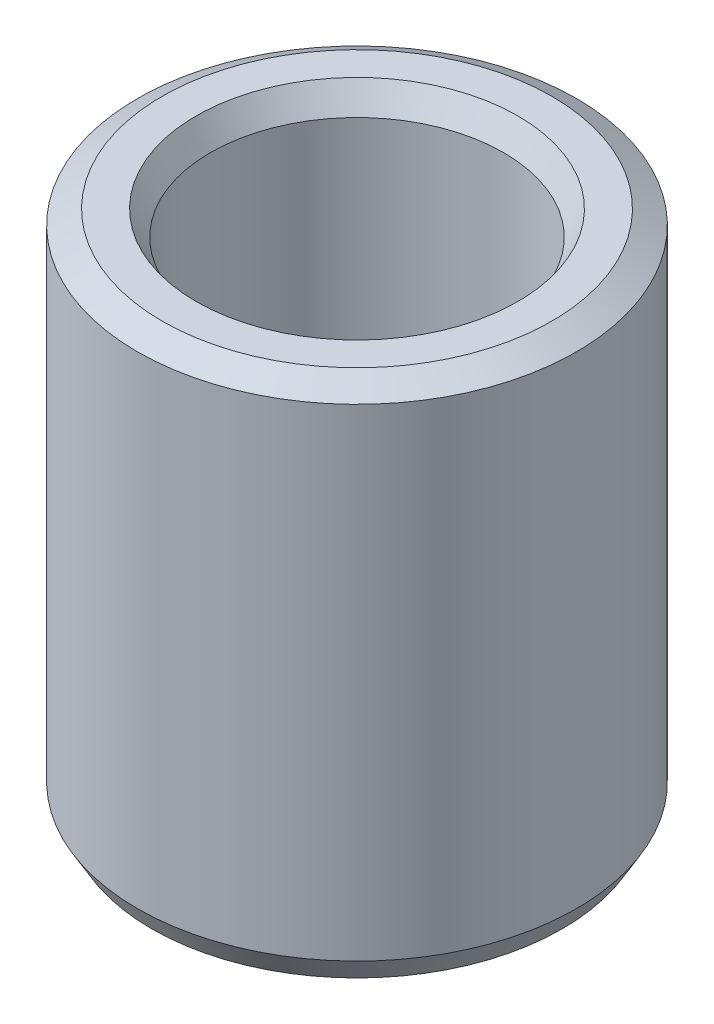
SolidWorks part; units mm, degrees
ref_plane "Front Plane" through (0, 0, 0) normal (0, 0, 1) x (1, 0, 0)
ref_plane "Top Plane" through (0, 0, 0) normal (0, 1, 0) x (1, 0, 0)
ref_plane "Right Plane" through (0, 0, 0) normal (1, 0, 0) x (0, 0, -1)
sketch "Sketch1" plane through (0, 0, 0) normal (0, 1, 0) x (1, 0, 0)
  circle A0 centre (0, 0) radius 35
  dimension "SLEEVE_OD" = 70
extrude "Boss-Extrude1" add sketch "Sketch1" along normal blind 83.103
sketch "Sketch2" plane through (0, 0, 0) normal (0, 1, 0) x (1, 0, 0)
  circle A0 centre (0, 0) radius 23.3777
  dimension "BORE_D" = 46.7554
extrude "Cut-Extrude1" cut sketch "Sketch2" along normal through all
chamfer "Chamfer1" distance 2.2712 angle 60 4 edges at (0, 83.103, 23.3777) (0, 0, 23.3777) (0, 0, 35) (0, 83.103, 35) first distance on face at (0, 83.103, 23.3777) first distance on face at (0, 0, 23.3777) first distance on face at (0, 83.103, 35)
